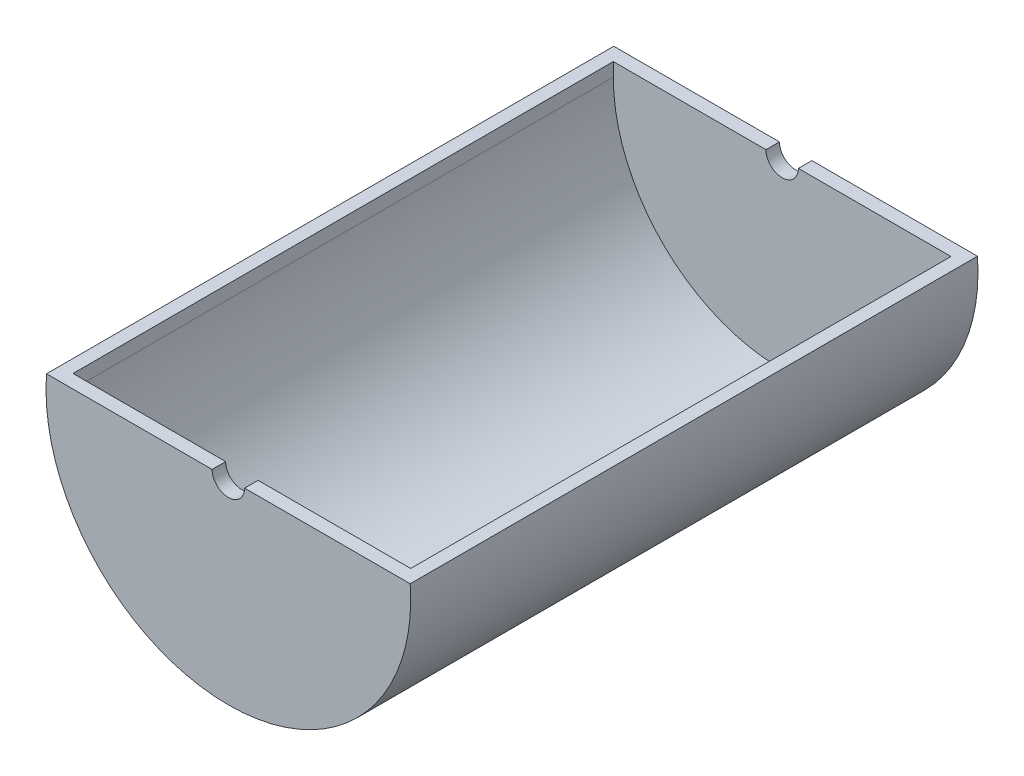
SolidWorks part; units mm, degrees
ref_plane "Front Plane" through (0, 0, 0) normal (0, 0, 1) x (1, 0, 0)
ref_plane "Top Plane" through (0, 0, 0) normal (0, 1, 0) x (1, 0, 0)
ref_plane "Right Plane" through (0, 0, 0) normal (1, 0, 0) x (0, 0, -1)
sketch "Sketch1" plane through (0, 0, 0) normal (0, 0, 1) x (1, 0, 0)
  line L1 (-134.6291, 10) -> (-125, 10)
  line L2 (-125, 0) -> (-125, 10)
  line L3 (125, 10) -> (125, 0)
  line L4 (-125, 0) -> (125, 0) construction
  line L5 (125, 10) -> (134.6291, 10)
  line L6 (-134.6291, 10) -> (134.6291, 10) construction
  arc A0 (-125, 0) -> (125, 0) centre (0, 0) ccw
  arc A1 (-134.6291, 10) -> (134.6291, 10) centre (0, 0) ccw
  dimension "D1" = 250
  dimension "D2" = 10
extrude "Boss-Extrude1" add sketch "Sketch1" along normal mid plane 420
sketch "Sketch2" plane through (0, 0, 0) normal (0, 0, 1) x (1, 0, 0)
  line L1 (-125, 10) -> (-12, 10)
  line L2 (12, 10) -> (125, 10)
  line L4 (134.6291, 10) -> (125, 10)
  line L5 (125, 10) -> (125, 0)
  line L6 (-125, 0) -> (-125, 10)
  line L7 (-125, 10) -> (-134.6291, 10)
  line L9 (125, 10) -> (125, 0)
  line L10 (-125, 0) -> (-125, 10)
  arc A0 (-12, 10) -> (12, 10) centre (0, 10) ccw
  arc A2 (-134.6291, 10) -> (134.6291, 10) centre (0, 0) ccw
  arc A3 (-125, 0) -> (125, 0) centre (0, 0) ccw
  arc A5 (-125, 0) -> (125, 0) centre (0, 0) ccw
  dimension "D2" = 24
  dimension "D1" = 0
extrude "Boss-Extrude2" add sketch "Sketch2" against normal blind 10 from surface starting at face at (0, -38.3333, 210)
extrude "Boss-Extrude3" add sketch "Sketch2<2>" along normal blind 10 from surface starting at face at (0, -38.3333, -210)
sketch "Sketch2<2>" plane through (0, 0, 0) normal (0, 0, 1) x (1, 0, 0) same geometry as "Sketch2"
